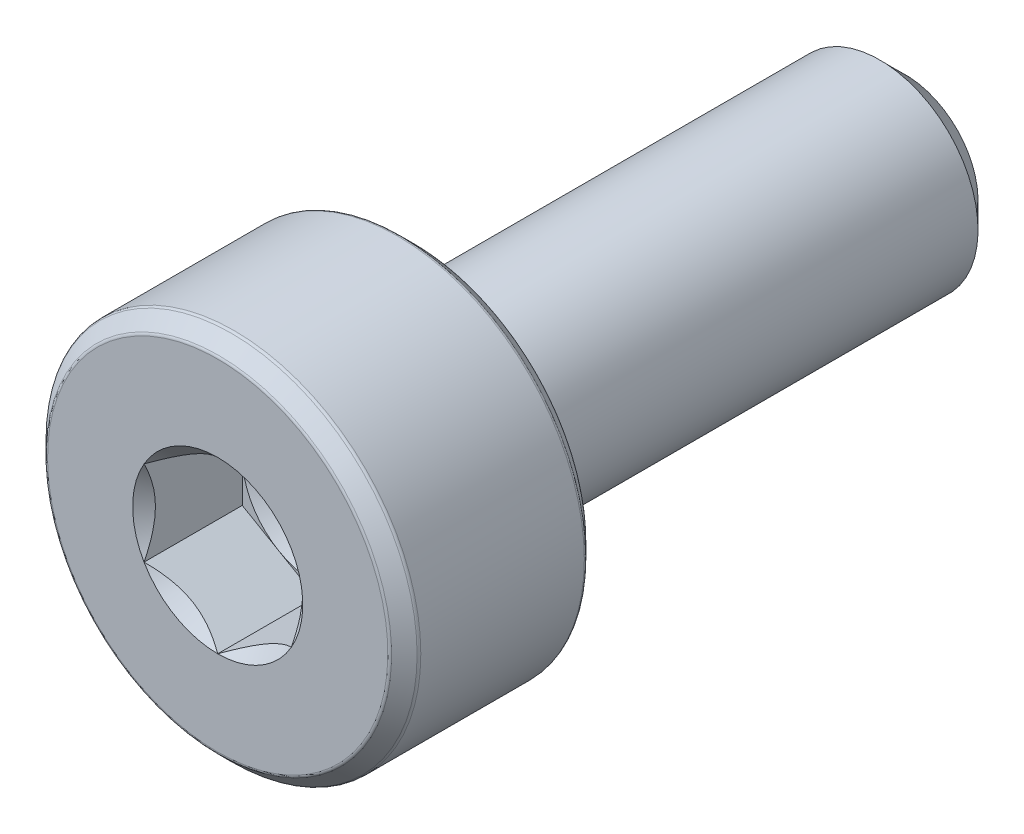
SolidWorks part; units mm, degrees
material "Alloy Steel"
ref_plane "Front Plane" through (0, 0, 0) normal (0, 0, 1) x (1, 0, 0)
ref_plane "Top Plane" through (0, 0, 0) normal (0, 1, 0) x (1, 0, 0)
ref_plane "Right Plane" through (0, 0, 0) normal (1, 0, 0) x (0, 0, -1)
sketch "Sketch1" plane through (0, 0, 0) normal (1, 0, 0) x (0, 0, -1)
  line L0 (-3.5, 0) -> (3.5, 0) construction
  line L1 (-3.5, 0) -> (-3.5, 1.9)
  line L2 (-3.5, 1.9) -> (-1.5, 1.9)
  line L3 (-1.5, 1.9) -> (-1.5, 1)
  line L4 (-1.5, 1) -> (3.2402, 1)
  line L5 (3.475, 1.0433) -> (3.675, 0.6969) construction
  line L6 (3.675, 0.6969) -> (3.875, 1.0433) construction
  line L7 (3.875, 1.0433) -> (3.475, 1.0433) construction
  line L8 (3.2402, 1) -> (3.5, 0.7402)
  line L9 (3.5, 0.7402) -> (3.5, 0)
  line L10 (3.5, 1) -> (3.85, 1) construction
  line L11 (3.675, 1.0433) -> (3.675, 1) construction
  line L12 (3.675, 1) -> (3.675, 0.7402) construction
  line L13 (3.675, 0.7402) -> (3.675, 0.6969) construction
  line L14 (3.65, 0.7402) -> (3.7, 0.7402)
  line L15 (3.4875, 1.0217) -> (3.8625, 1.0217)
  line L16 (3.7, 0.7402) -> (3.8625, 1.0217)
  line L17 (3.65, 0.7402) -> (3.4875, 1.0217)
  line L18 (-3.5, 0.75) -> (-2.5, 0.75)
  line L19 (-2.5, 0.75) -> (-2.5, 0)
  line L20 (2.1, 1) -> (2.1, -1) construction
  point P20 (3.675, 1.0217)
  point P22 (2.1, -1)
  point P28 (2.1, 0)
  point P29 (3.2402, -1)
  dimension "Head Diameter" = 3.8
  dimension "Length" = 5
  dimension "Head Height" = 2
  dimension "D2" = 2
  dimension "D1" = 45
  dimension "Thread Pitch" = 0.4
  dimension "D3" = 0.05
  dimension "Drive Size" = 1.5
  dimension "D4" = 1.4
  dimension "D5" = 1
sketch "Sketch3" plane through (0, 0, 0) normal (1, 0, 0) x (0, 0, -1)
  line L0 (-3.5, 1.7323) -> (-3.5, 0.75)
  line L1 (-3.5, 0.75) -> (-2.5, 0.75)
  line L2 (-2.5, 0.75) -> (-2.5, 0)
  line L3 (-2.5, 0) -> (3.5, 0)
  line L4 (3.5, 0) -> (3.5, 0.7402)
  line L5 (3.5, 0.7402) -> (3.2402, 1)
  line L6 (3.2402, 1) -> (-1.5, 1)
  line L7 (-1.5, 1) -> (-1.5, 1.7323)
  line L8 (-1.6677, 1.9) -> (-3.3323, 1.9)
  line L9 (-3.4889, 1.7591) -> (-3.3591, 1.8889)
  line L10 (-1.6409, 1.8889) -> (-1.5111, 1.7591)
  line L11 (-3.5, 1.9) -> (-1.5, 1.9) construction
  arc A0 (-1.5111, 1.7591) -> (-1.5, 1.7323) centre (-1.538, 1.7323) cw
  arc A1 (-1.6409, 1.8889) -> (-1.6677, 1.9) centre (-1.6677, 1.862) ccw
  arc A2 (-3.3591, 1.8889) -> (-3.3323, 1.9) centre (-3.3323, 1.862) cw
  arc A3 (-3.4889, 1.7591) -> (-3.5, 1.7323) centre (-3.462, 1.7323) ccw
  point P29 (-3.5, 1.748)
  dimension "D3" = 0.038
  dimension "D1" = 45
  dimension "D2" = 0.152
revolve "Revolve1" add sketch "Sketch3" angle 360 about L0
sketch "Sketch4" plane through (0, 0, 3.5) normal (0, 0, 1) x (1, 0, 0)
  line L1 (0, 0.866) -> (-0.75, 0.433)
  line L2 (-0.75, 0.433) -> (-0.75, -0.433)
  line L3 (-0.75, -0.433) -> (0, -0.866)
  line L4 (0, -0.866) -> (0.75, -0.433)
  line L5 (0.75, -0.433) -> (0.75, 0.433)
  line L6 (0.75, 0.433) -> (0, 0.866)
  circle A0 centre (0, 0) radius 0.75 construction
extrude "Cut-Extrude1" cut sketch "Sketch4" against normal up to vertex (1 mm away) up to point (0, 0.75, 2.5)
sketch "Sketch5" plane through (0, 0, 3.5) normal (0, 0, 1) x (1, 0, 0)
  circle A0 centre (0, 0) radius 0.866
extrude "Cut-Extrude2" cut sketch "Sketch5" against normal up to next (1 mm away) draft 45
sketch "Sketch10" plane through (0, 0, 2.5) normal (0, 0, 1) x (1, 0, 0)
  line L0 (0.75, 0.433) -> (0.75, -0.433) construction
  circle A0 centre (0, 0) radius 0.75
extrude "Cut-Extrude3" cut sketch "Sketch10" against normal through all draft 60
split "Split1" [suppressed] bodies to split 112
sketch "Sketch6" [suppressed] plane through (0, 0, -3.5) normal (0, 0, -1) x (-1, 0, 0)
  circle A0 centre (0, 0) radius 1 construction
  circle A1 centre (0, 0) radius 1
curve "Helix/Spiral1" [suppressed] pitch 0.4 height 5.4 turns 13.5
sketch "Sketch7" [suppressed] plane through (0, 0, 0) normal (1, 0, 0) x (0, 0, -1)
  line L0 (3.65, 0.7402) -> (3.7, 0.7402) construction
  line L1 (3.65, 0.7402) -> (3.4875, 1.0217) construction
  line L2 (3.4875, 1.0217) -> (3.8625, 1.0217) construction
  line L3 (3.7, 0.7402) -> (3.8625, 1.0217) construction
  line L4 (3.65, 0.7402) -> (3.7, 0.7402)
  line L5 (3.65, 0.7402) -> (3.4875, 1.0217)
  line L6 (3.4875, 1.0217) -> (3.8625, 1.0217)
  line L7 (3.7, 0.7402) -> (3.8625, 1.0217)
sweep "Cut-Sweep1" [suppressed] cut profiles "Sketch7" path "Helix/Spiral1"
sketch "Sketch11" [suppressed] plane through (0, 0, 0) normal (1, 0, 0) x (0, 0, -1)
  line L0 (-1.5, 1.1) -> (-1.4, 1) construction
  line L1 (-1.5, 1.9) -> (-1.5, 1) construction
  line L2 (-1.5, 1) -> (3.2402, 1) construction
  line L3 (-1.4, 1) -> (-1.1, 1)
  line L4 (-1.1, 1) -> (-0.1, 0)
  line L5 (-3.5, 0) -> (3.5, 0) construction
  line L6 (-0.1, 0) -> (-1.5, 0)
  line L7 (-1.5, 0) -> (-1.5, 1.1)
  line L8 (-1.5, -1.748) -> (-1.5, 1.748) construction
  arc A0 (-1.4, 1) -> (-1.5, 1.1) centre (-1.4, 1.1) cw
  dimension "D4" = 0.4
  dimension "D1" = 45
  dimension "D2" = 0.1
  dimension "D3" = 45
revolve "Revolve2" [suppressed] add sketch "Sketch11" angle 360 about L6
sketch "Sketch12" [suppressed] plane through (0, 0, 3.5) normal (0, 0, 1) x (1, 0, 0)
  line L0 (0, 0) -> (0, 1.9) construction
  line L1 (0, 0) -> (0.095, 2.0101) construction
  line L2 (0.095, 2.0101) -> (-0.095, 2.0101)
  line L3 (-0.095, 2.0101) -> (0, 0) construction
  line L4 (-0.095, 2.0101) -> (-0.0042, 1.8432)
  line L5 (0.0042, 1.8432) -> (0.095, 2.0101)
  line L7 (0, 1.7323) -> (0, 1.7591) construction
  circle A0 centre (0, 0) radius 1.9 construction
  arc A2 (-0.0042, 1.8432) -> (0.0042, 1.8432) centre (0, 1.8454) ccw
  point P11 (0, 1.8355)
  point P13 (0, 1.7457)
  point P15 (0, 1.8407)
  dimension "D3" = 0.0048
  dimension "D1" = 0.19
  dimension "D2" = 5.412
  dimension "D4" = 0.095
extrude "Cut-Extrude4" [suppressed] cut sketch "Sketch12" against normal up to vertex
sketch "Sketch13" [suppressed] plane through (0, 0, 2.5) normal (0, 0, 1) x (1, 0, 0)
  circle A0 centre (0, 0) radius 1.9
  circle A2 centre (0, 0) radius 1
  arc A3 (0.0349, 1.8997) -> (-0.0349, 1.8997) centre (0, 0) ccw construction
extrude "Boss-Extrude1" [suppressed] add sketch "Sketch13" along normal through all draft 45
fillet "Fillet1" [suppressed] radius 0.0125
pattern_circular "CirPattern1" [suppressed] count 98 over 360 of bodies 116
equation "\"D3@Sketch1\" = \"Thread Pitch@Sketch1\" / 8"
equation "\"D4@Sketch1\" = \"Thread Pitch@Sketch1\" * 3.5"
equation "\"D3@Helix/Spiral1\" = \"Length@Sketch1\" + \"Thread Pitch@Sketch1\""
equation "\"D4@Helix/Spiral1\" = \"Thread Pitch@Sketch1\""
equation "\"D5@Sketch1\"=\"Head Height@Sketch1\"*0.5"
equation "\"D2@Sketch3\"=\"Head Diameter@Sketch1\" /25"
equation "\"D2@Sketch11\"=\"Thread Pitch@Sketch1\" / 4"
equation "\"D1@Sketch12\"=\"Head Diameter@Sketch1\"*0.05"
equation "\"D1@CirPattern1\"=int(360/(\"D2@Sketch12\"*.675))"
equation "\"D3@Sketch12\"=\"D1@Sketch12\"*00.025"
equation "\"D4@Sketch11\"=\"Thread Pitch@Sketch1\" "
equation "\"D3@Sketch3\"=\"D2@Sketch3\"*0.25"
equation "\"D4@Sketch12\"= \"D2@Sketch3\"*0.625"
